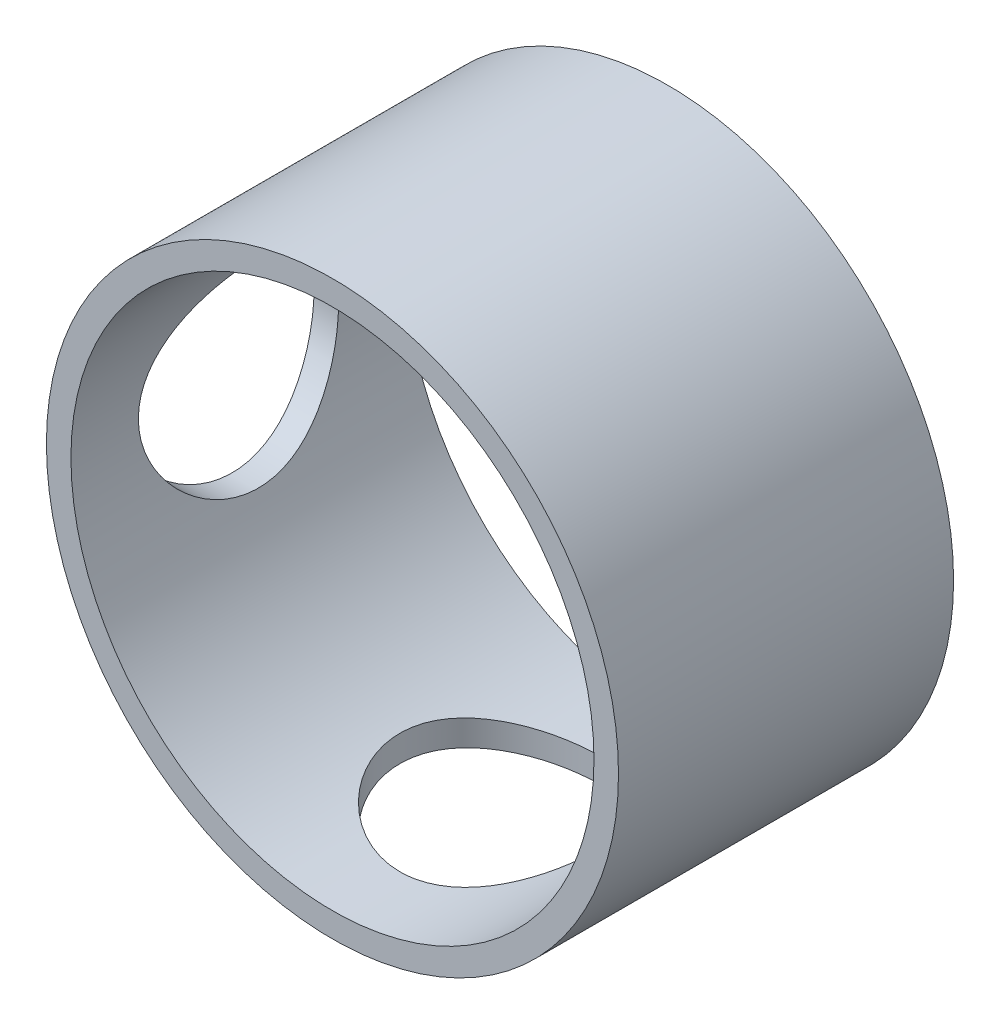
SolidWorks part; units mm, degrees
material "Acrylic (Medium-high impact)"
ref_plane "Front Plane" through (0, 0, 0) normal (0, 0, 1) x (1, 0, 0)
ref_plane "Top Plane" through (0, 0, 0) normal (0, 1, 0) x (1, 0, 0)
ref_plane "Right Plane" through (0, 0, 0) normal (1, 0, 0) x (0, 0, -1)
sketch "Sketch1" plane through (0, 0, 0) normal (0, 0, 1) x (1, 0, 0)
  circle A0 centre (0, 0) radius 35
  circle A1 centre (0, 0) radius 32
  dimension "D1" = 64
  dimension "D2" = 70
extrude "Boss-Extrude1" add sketch "Sketch1" along normal blind 20.5 and the other way blind 20.5
sketch "Sketch5" plane through (0, 0, 0) normal (1, 0, 0) x (0, 0, -1)
  circle A0 centre (0, 0) radius 12.25
  dimension "D1" = 24.5
extrude "Cut-Extrude2" cut sketch "Sketch5" against normal through all
sketch "Sketch6" plane through (0, 0, 0) normal (0, 1, 0) x (1, 0, 0)
  circle A0 centre (0, 0) radius 12.25
  dimension "D1" = 24.5
extrude "Cut-Extrude3" cut sketch "Sketch6" against normal through all
